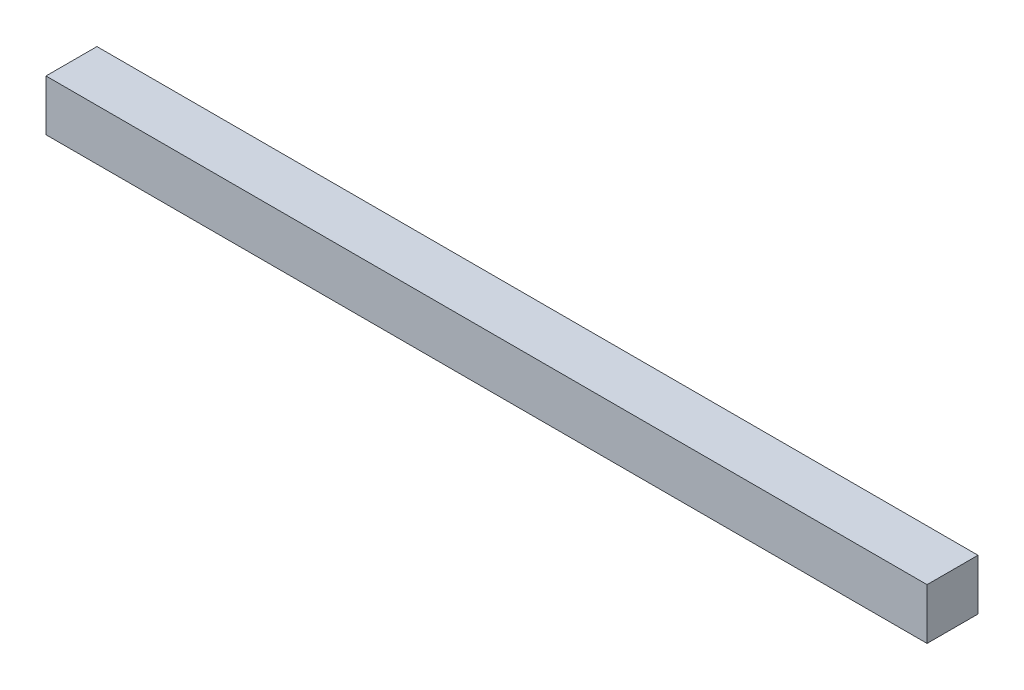
SolidWorks part; units mm, degrees
ref_plane "Plan de face" through (0, 0, 0) normal (0, 0, 1) x (1, 0, 0)
ref_plane "Plan de dessus" through (0, 0, 0) normal (0, 1, 0) x (1, 0, 0)
ref_plane "Plan de droite" through (0, 0, 0) normal (1, 0, 0) x (0, 0, -1)
sketch "Esquisse1" plane through (0, 0, 0) normal (0, 0, 1) x (1, 0, 0)
  line L1 (-217.8166, 74.7917) -> (-44.8166, 74.7917)
  line L2 (-217.8166, 74.7917) -> (-217.8166, 64.7917)
  line L3 (-217.8166, 64.7917) -> (-44.8166, 64.7917)
  line L4 (-44.8166, 74.7917) -> (-44.8166, 64.7917)
  dimension "D1" = 10
  dimension "D2" = 173
extrude "Boss.-Extru.1" add sketch "Esquisse1" along normal blind 10 contours L1 L4 L3 L2
equation "\"EpaisseurPlaque\"= 3"
equation "\"ProfondeurBoite\"=460"
equation "\"LongueurSyphon\"=170"
equation "\"LargeurSyphon\"=120"
equation "\"HauteurCoteDroit\"= 490"
equation "\"HauteurCoteGauche\"= 540"
equation "\"HauteurSolSyphon\"= 300"
equation "\"HauteurSyphon\"=\"HauteurCoteGauche\"-\"HauteurSolSyphon\""
equation "\"LargeurDroite\"=10"
equation "\"LargeurGauche\"=150"
equation "\"LargeurBoite\"= \"LargeurDroite\" + \"LargeurGauche\" + \"LargeurSyphon\""
equation "\"D2@Esquisse1\"=\"LongueurSyphon\" +3"
